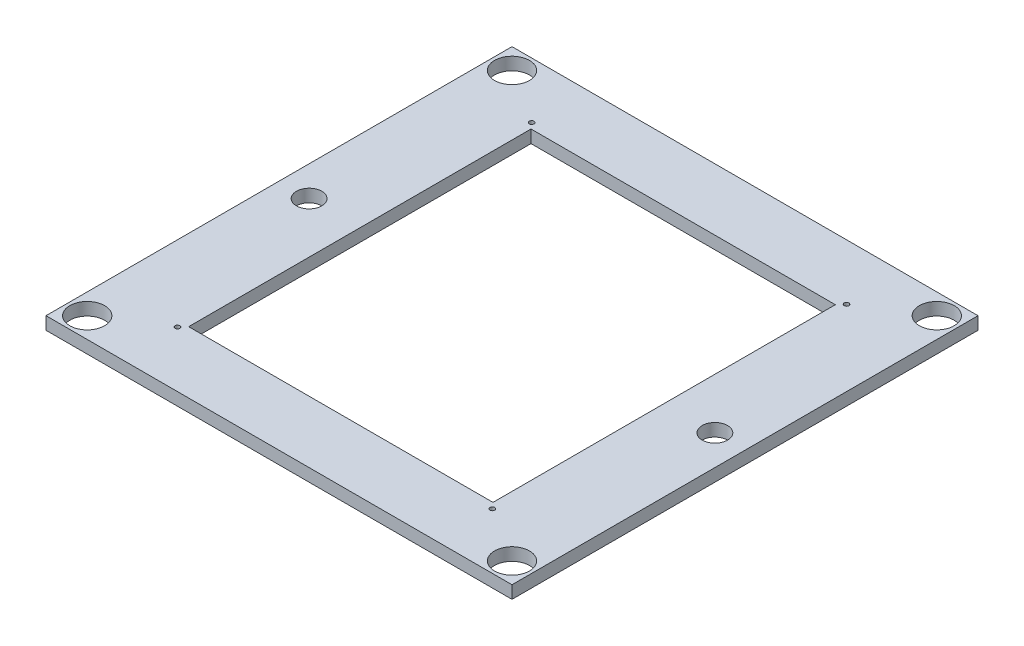
SolidWorks part; units mm, degrees
ref_plane "Front Plane" through (0, 0, 0) normal (0, 0, 1) x (1, 0, 0)
ref_plane "Top Plane" through (0, 0, 0) normal (0, 1, 0) x (1, 0, 0)
ref_plane "Right Plane" through (0, 0, 0) normal (1, 0, 0) x (0, 0, -1)
sketch "Sketch1" plane through (0, 0, 0) normal (0, 1, 0) x (1, 0, 0)
  line L0 (147, 147) -> (147, -147)
  line L1 (-147, -147) -> (147, -147)
  line L2 (-147, -147) -> (-147, 147)
  line L3 (-147, 147) -> (147, 147)
  line L5 (-147, -147) -> (147, 147) construction
  line L6 (-147, 147) -> (147, -147) construction
  line L7 (-96, -108) -> (96, -108)
  line L8 (-96, -108) -> (-96, 108)
  line L9 (-96, 108) -> (96, 108)
  line L10 (96, -108) -> (96, 108)
  line L11 (-96, -108) -> (96, 108) construction
  line L12 (-96, 108) -> (96, -108) construction
  point P0 (0, 0)
  point P5 (0, 0)
  dimension "D1" = 294
  dimension "D2" = 192
  dimension "D3" = 216
extrude "Boss-Extrude1" add sketch "Sketch1" along normal blind 8
sketch "Sketch2" plane through (0, 0, 0) normal (0, 1, 0) x (1, 0, 0)
  line L1 (147, 147) -> (-147, 147) construction
  line L2 (147, -147) -> (147, 147) construction
  circle A0 centre (134, 134) radius 11
  dimension "D1" = 22
  dimension "D2" = 13
  dimension "D3" = 13
extrude "Cut-Extrude1" cut sketch "Sketch2" along normal through all
sketch "Sketch4" plane through (0, 8, 0) normal (0, 1, 0) x (1, 0, 0)
  line L0 (134, -864) -> (134, 49136) construction
  circle A0 centre (128, 0) radius 8
  dimension "D1" = 6
  dimension "D2" = 16
mirror "Mirror2" about plane through (0, 0, 0) normal (0, 0, 1) of "Cut-Extrude1"
extrude "Cut-Extrude2" cut sketch "Sketch4" against normal through all
mirror "Mirror3" about plane through (0, 0, 0) normal (1, 0, 0) of "Mirror2", "Cut-Extrude1"
mirror "Mirror4" about plane through (0, 0, 0) normal (1, 0, 0) of "Cut-Extrude2"
sketch "Sketch5" plane through (0, 8, 0) normal (0, 1, 0) x (1, 0, 0)
  line L0 (-96, 108) -> (96, -108)
  line L1 (96, -108) -> (99.3218, -111.737)
  line L2 (-96, 108) -> (-99.3218, 111.737)
  line L4 (99.3218, -111.737) -> (-99.3218, -111.737)
  line L5 (99.3218, -111.737) -> (99.3218, 111.737)
  line L6 (99.3218, 111.737) -> (-99.3218, 111.737)
  line L7 (-99.3218, -111.737) -> (-99.3218, 111.737)
  circle A0 centre (99.3218, 111.737) radius 1.5
  circle A1 centre (-99.3218, 111.737) radius 1.5
  circle A2 centre (-99.3218, -111.737) radius 1.5
  circle A3 centre (99.3218, -111.737) radius 1.5
  dimension "D3" = 3
  dimension "D4" = 3
  dimension "D5" = 3
  dimension "D6" = 3
  dimension "D1" = 5
  dimension "D2" = 5
extrude "Cut-Extrude3" cut sketch "Sketch5" against normal through all contours L5 A0 L6 | L6 A0 L5 | L6 A1 L7 | L2 A1 L6 | L7 A1 L2 | L7 A2 L4 | L4 A2 L7 | L4 A3 L5 | L1 A3 L4 | L5 A3 L1 region at (-98.9742, 8, -110.8228) region at (-98.4364, 8, -111.3394) region at (98.9742, 8, 110.8228) region at (98.4364, 8, 111.3394) region at (-99.534, 8, -111.9493) region at (99.534, 8, 111.9493) region at (-98.6852, 8, 111.1004) region at (-99.534, 8, 111.9493) region at (99.534, 8, -111.9493) region at (98.6852, 8, -111.1004)
equation "\"D5@Sketch5\"=\"D4@Sketch5\""
equation "\"D3@Sketch5\"=\"D4@Sketch5\""
equation "\"D6@Sketch5\"=\"D4@Sketch5\""
